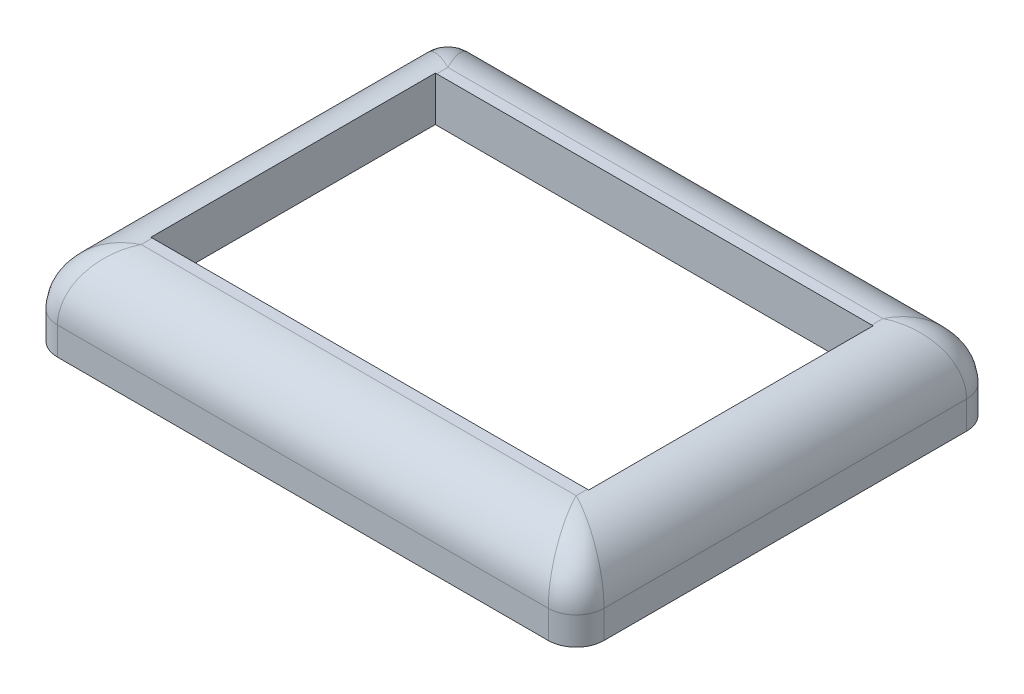
SolidWorks part; units mm, degrees
ref_plane "Спереди" through (0, 0, 0) normal (0, 0, 1) x (1, 0, 0)
ref_plane "Сверху" through (0, 0, 0) normal (0, 1, 0) x (1, 0, 0)
ref_plane "Справа" through (0, 0, 0) normal (1, 0, 0) x (0, 0, -1)
sketch "Эскиз1" plane through (0, 0, 0) normal (0, 1, 0) x (1, 0, 0)
  line L0 (0, -1000) -> (0, 49000) construction
  line L1 (39.25, -1000) -> (39.25, 49000) construction
  line L2 (-39.25, -1000) -> (-39.25, 49000) construction
  line L3 (-1000, 0) -> (49000, 0) construction
  line L4 (-1000, -25.5) -> (49000, -25.5) construction
  line L5 (-1000, 25.5) -> (49000, 25.5) construction
  line L6 (49, -1000) -> (49, 49000) construction
  line L7 (-49, -1000) -> (-49, 49000) construction
  line L8 (-1000, -37.5) -> (49000, -37.5) construction
  line L9 (-1000, 37.5) -> (49000, 37.5) construction
  line L10 (-49, 37.5) -> (-49, -37.5)
  line L11 (-49, -37.5) -> (49, -37.5)
  line L12 (49, -37.5) -> (49, 37.5)
  line L13 (49, 37.5) -> (-49, 37.5)
  line L14 (-39.25, 25.5) -> (-39.25, -25.5)
  line L15 (-39.25, -25.5) -> (39.25, -25.5)
  line L16 (39.25, -25.5) -> (39.25, 25.5)
  line L17 (39.25, 25.5) -> (-39.25, 25.5)
  line L18 (49, -1000) -> (49, 49000) construction
extrude "Бобышка-Вытянуть1" add sketch "Эскиз1" along normal blind 15
sketch "Эскиз2" plane through (0, 0, 0) normal (0, -1, 0) x (1, 0, 0)
  line L0 (-1000, 0) -> (49000, 0) construction
  line L1 (-1000, -35) -> (49000, -35) construction
  line L2 (-1000, 35) -> (49000, 35) construction
  line L3 (0, -1000) -> (0, 49000) construction
  line L4 (46.5, -1000) -> (46.5, 49000) construction
  line L5 (-46.5, -1000) -> (-46.5, 49000) construction
  line L6 (-46.5, 35) -> (-46.5, -35)
  line L7 (-46.5, -35) -> (46.5, -35)
  line L8 (46.5, -35) -> (46.5, 35)
  line L9 (46.5, 35) -> (-46.5, 35)
extrude "Вырез-Вытянуть1" cut sketch "Эскиз2" against normal blind 7
fillet "Скругление1" radius 10 4 edges at (0, 15, -37.5) (49, 15, 0) (0, 15, 37.5) (-49, 15, 0)
fillet "Скругление2" radius 5 8 edges at (49, 2.5, 37.5) (46.0711, 12.0711, -34.5711) (-46.0711, 12.0711, 34.5711) (-46.0711, 12.0711, -34.5711) (46.0711, 12.0711, 34.5711) (49, 2.5, -37.5) (-49, 2.5, 37.5) (-49, 2.5, -37.5)
sketch "Эскиз3" plane through (0, 7, 0) normal (0, -1, 0) x (1, 0, 0)
  line L0 (-1000, 0) -> (49000, 0) construction
  line L1 (0, -1000) -> (0, 49000) construction
  line L2 (43.5, -1000) -> (43.5, 49000) construction
  line L3 (-43.5, -1000) -> (-43.5, 49000) construction
  line L4 (-1000, -32.5) -> (49000, -32.5) construction
  line L5 (-1000, 32.5) -> (49000, 32.5) construction
  line L6 (-1041.0437, 35) -> (48958.9563, 35) construction
  line L8 (-1043.5, 33.5) -> (48956.5, 33.5) construction
  circle A0 centre (-43.5, 32.5) radius 1
  circle A1 centre (43.5, 32.5) radius 1
  circle A2 centre (-43.5, -32.5) radius 1
  circle A3 centre (43.5, -32.5) radius 1
extrude "Вырез-Вытянуть2" cut sketch "Эскиз3" against normal blind 5
sketch "Эскиз4" plane through (0, 7, 0) normal (0, -1, 0) x (1, 0, 0)
  line L0 (39.25, -974.5) -> (39.25, 49025.5) construction
  line L1 (45.25, -974.5) -> (45.25, 49025.5) construction
  line L2 (39.25, 25.5) -> (45.25, 25.5)
  line L3 (45.25, 25.5) -> (45.25, -25.5)
  line L4 (45.25, -25.5) -> (39.25, -25.5)
  line L5 (39.25, -25.5) -> (39.25, 25.5)
extrude "Вырез-Вытянуть3" cut sketch "Эскиз4" against normal blind 4
sketch "Эскиз5" plane through (0, 0, 0) normal (0, -1, 0) x (1, 0, 0)
  line L0 (-1042.088, 37.5) -> (48957.912, 37.5) construction
  line L1 (-47.75, -975.643) -> (-47.75, 49024.357) construction
  line L2 (-1042.3317, 35) -> (48957.6683, 35) construction
  line L3 (-1026.5815, -36.25) -> (48973.4185, -36.25) construction
  line L4 (-1042.3317, 36.25) -> (48957.6683, 36.25) construction
  line L5 (-46.5, -975.643) -> (-46.5, 49024.357) construction
  line L6 (47.75, -982.2929) -> (47.75, 49017.7071) construction
  line L7 (46.5, -982.2929) -> (46.5, 49017.7071) construction
  line L8 (-47.75, -33.25) -> (-47.75, 33.25)
  line L9 (-1026.5815, -35) -> (48973.4185, -35) construction
  line L10 (-44.75, 36.25) -> (44.75, 36.25)
  line L11 (47.75, 33.25) -> (47.75, -33.25)
  line L12 (44.75, -36.25) -> (-44.75, -36.25)
  circle A1 centre (44.75, 33.25) radius 3 construction
  circle A2 centre (-44.75, 33.25) radius 3 construction
  circle A3 centre (44.75, -33.25) radius 3 construction
  circle A4 centre (-44.75, -33.25) radius 3 construction
  arc A5 (-47.75, -33.25) -> (-44.75, -36.25) centre (-44.75, -33.25) ccw
  arc A6 (-44.75, 36.25) -> (-47.75, 33.25) centre (-44.75, 33.25) ccw
  arc A7 (44.75, 36.25) -> (47.75, 33.25) centre (44.75, 33.25) cw
  arc A8 (47.75, -33.25) -> (44.75, -36.25) centre (44.75, -33.25) cw
  dimension "D3" = 1.25
extrude "Вырез-Вытянуть4" cut sketch "Эскиз5" against normal blind 2
